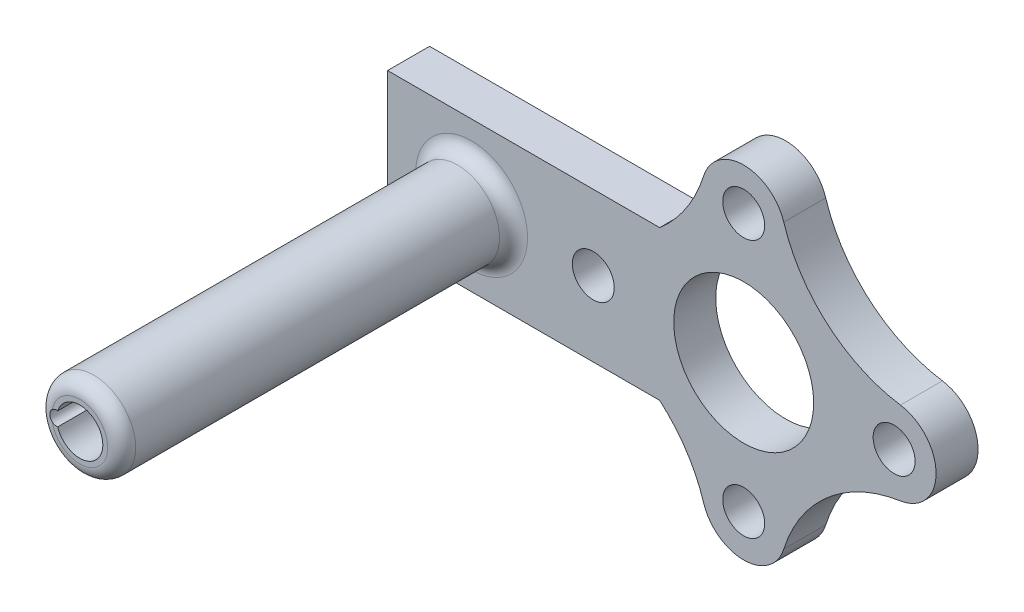
SolidWorks part; units mm, degrees
other "Markup1"
sketch "Sketch6" plane through (-25.45, 12.225, 0) normal (-0.2164, 0.2815, -0.9348) x (-0.9689, 0.0561, 0.2412)
ref_plane "Front Plane" through (0, 0, 0) normal (0, 0, 1) x (1, 0, 0)
ref_plane "Top Plane" through (0, 0, 0) normal (0, 1, 0) x (1, 0, 0)
ref_plane "Right Plane" through (0, 0, 0) normal (1, 0, 0) x (0, 0, -1)
sketch "Sketch1" plane through (0, 0, 0) normal (0, 0, 1) x (1, 0, 0)
  line L0 (-10.75, 0) -> (10.75, 0) construction
  line L1 (0, -9.225) -> (0, 9.225) construction
  circle A0 centre (0, 0) radius 5
  circle A1 centre (0, 9.225) radius 1.5
  circle A2 centre (10.75, 0) radius 1.5
  circle A3 centre (0, -9.225) radius 1.5
  circle A4 centre (-10.75, 0) radius 1.5
  circle A5 centre (0, 9.225) radius 3
  circle A6 centre (10.75, 0) radius 3
  arc A7 (-2.8635, -10.1195) -> (2.8635, -10.1195) centre (0, -9.225) ccw
  circle A8 centre (-10.75, 0) radius 3
  circle A9 centre (0, 0) radius 8 construction
  arc A10 (-11.1994, 2.9661) -> (-2.8635, 10.1195) centre (-12.7512, 13.2081) ccw
  arc A11 (2.8635, 10.1195) -> (11.1994, 2.9661) centre (12.7512, 13.2081) ccw
  arc A12 (11.1994, -2.9661) -> (2.8635, -10.1195) centre (12.7512, -13.2081) ccw
  arc A13 (-2.8635, -10.1195) -> (-11.1994, -2.9661) centre (-12.7512, -13.2081) ccw
  point P6 (0, 0)
  point P9 (0, 0)
  dimension "D1" = 10
  dimension "D4" = 3
  dimension "D5" = 6
  dimension "D2" = 21.5
  dimension "D3" = 18.45
  dimension "D6" = 3
extrude "Boss-Extrude1" add sketch "Sketch1" along normal blind 3 contours A13 A7 A12 A6 A11 A5 A10 A8 A3 A0 | A5 A1 | A8 A4 | A6 A2 region at (-0.4396, 6.3432, 0) region at (2.997, 9.6822, 0) region at (12.9603, 1.9007, 0) region at (-8.8493, 2.2103, 0)
sketch "Sketch2" plane through (0, 0, 0) normal (0, 0, -1) x (-1, 0, 0)
  line L0 (6.0053, 5.3469) -> (6.0053, -5.3469)
  line L1 (6.0053, 5.3469) -> (25.45, 5.3469)
  line L2 (6.0053, -5.3469) -> (25.45, -5.3469)
  line L3 (25.45, 5.3469) -> (25.45, -5.3469)
  arc A0 (2.8635, 10.1195) -> (11.1994, 2.9661) centre (12.7512, 13.2081) ccw construction
  arc A1 (11.1994, -2.9661) -> (2.8635, -10.1195) centre (12.7512, -13.2081) ccw construction
  circle A2 centre (19.45, 0) radius 3
  circle A3 centre (10.75, 0) radius 1.5 construction
  circle A4 centre (10.75, 0) radius 1.5
  dimension "D1" = 19.45
  dimension "D3" = 6
  dimension "D2" = 6
extrude "Boss-Extrude2" add sketch "Sketch2" against normal through all
sketch "Sketch3" plane through (0, 0, 3) normal (0, 0, 1) x (1, 0, 0)
  circle A0 centre (-19.45, 0) radius 3
  circle A1 centre (-19.45, 0) radius 1.65
  dimension "D1" = 6
  dimension "D2" = 3.3
extrude "Boss-Extrude3" add sketch "Sketch3" along normal blind 28 and the other way through all
sketch "Sketch4" plane through (0, 0, 31) normal (0, 0, 1) x (1, 0, 0)
  circle A0 centre (-21.1, 0) radius 0.5
  circle A1 centre (-19.45, 0) radius 1.65 construction
  dimension "D1" = 1
extrude "Cut-Extrude1" cut sketch "Sketch4" against normal blind 30
sketch "Sketch5" plane through (0, 0, 0) normal (0, 0, -1) x (-1, 0, 0)
  circle A0 centre (19.45, 0) radius 3
  dimension "D1" = 6
extrude "Cut-Extrude2" cut sketch "Sketch5" against normal blind 2
chamfer "Chamfer1" distance 1 angle 45 1 edges at (-22.45, 0, 2)
fillet "Fillet2" radius 1 1 edges at (-16.45, 0, 3)
fillet "Fillet3" radius 1 1 edges at (-16.45, 0, 31)
